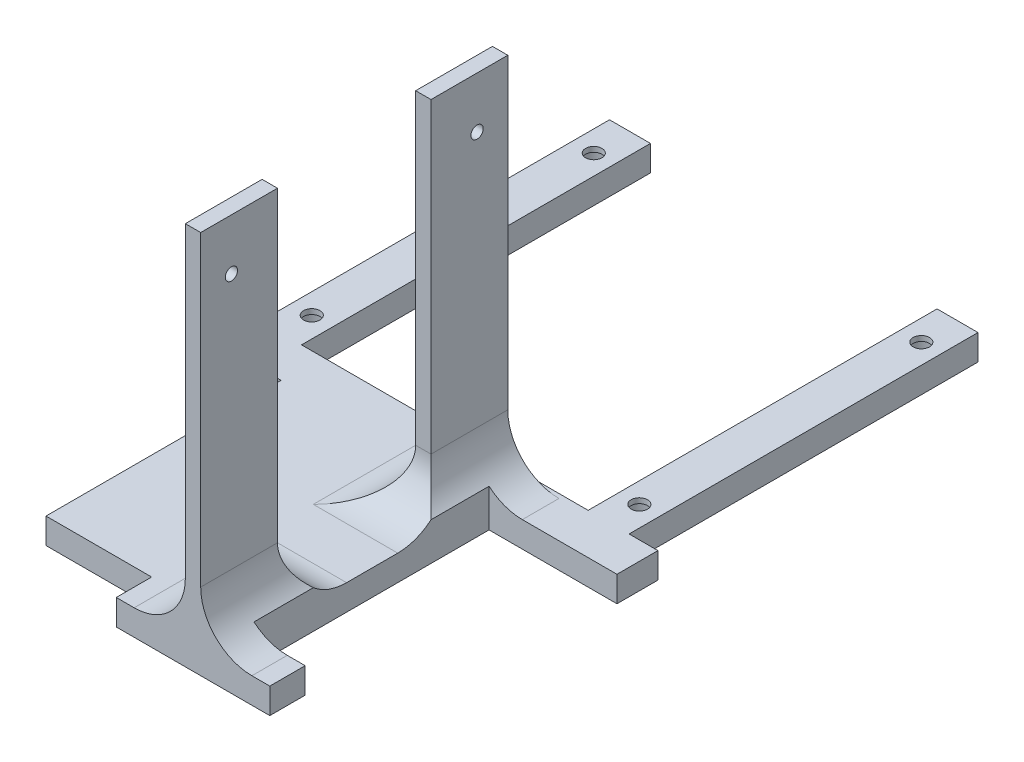
SolidWorks part; units mm, degrees
ref_plane "Front Plane" through (0, 0, 0) normal (0, 0, 1) x (1, 0, 0)
ref_plane "Top Plane" through (0, 0, 0) normal (0, 1, 0) x (1, 0, 0)
ref_plane "Right Plane" through (0, 0, 0) normal (1, 0, 0) x (0, 0, -1)
sketch "Sketch1" plane through (0, 0, 0) normal (0, 1, 0) x (1, 0, 0)
  line L0 (5, 22.8413) -> (16.3601, 22.8413)
  line L4 (5, 22.8413) -> (5, -23.0883)
  line L6 (-35.6399, 22.8413) -> (-35.6399, -23.0883)
  line L15 (-15, -30) -> (15, -30)
  line L16 (-15, -30) -> (-15, -23.0883)
  line L18 (15, -30) -> (15, -23.0883)
  line L19 (5, -23.0883) -> (15, -23.0883)
  line L20 (-35.6399, -23.0883) -> (-15, -23.0883)
  line L26 (-44.0081, 22.8413) -> (-35.6399, 22.8413)
  line L27 (16.3601, 22.8413) -> (29.9919, 22.8413)
  line L28 (29.9919, 22.8413) -> (29.9919, 30.01)
  line L29 (-44.0081, 22.8413) -> (-51.6409, 22.8413)
  line L30 (-51.6409, 22.8413) -> (-51.6409, 30.8413)
  line L31 (-51.6409, 30.8413) -> (-47.6409, 30.8413)
  line L32 (29.9919, 30.8413) -> (29.9919, 30.01)
  line L33 (-39.6409, 30.8413) -> (16.3601, 30.8413)
  line L35 (-47.6409, 30.8413) -> (-47.6409, 88.1003)
  line L37 (-39.6409, 30.8413) -> (-39.6409, 88.1003)
  line L39 (16.3601, 30.8413) -> (16.3601, 92.1003)
  line L41 (24.3591, 30.8413) -> (24.3591, 92.1003)
  line L42 (24.3591, 30.8413) -> (29.9919, 30.8413)
  line L46 (16.3601, 92.1003) -> (16.3601, 99.0177)
  line L47 (16.3601, 99.0177) -> (24.3591, 99.0177)
  line L48 (24.3591, 99.0177) -> (24.3591, 92.1003)
  line L49 (-47.6409, 88.1003) -> (-47.6409, 99.0177)
  line L50 (-47.6409, 99.0177) -> (-39.6409, 99.0177)
  line L51 (-39.6409, 99.0177) -> (-39.6409, 88.1003)
  circle A0 centre (-43.5402, 91.8413) radius 1.6
  circle A1 centre (20.4598, 91.8413) radius 1.6
  circle A2 centre (-43.6409, 36.8413) radius 1.6
  circle A3 centre (20.3591, 36.8413) radius 1.6
  point P0 (0, 0)
  dimension "D1" = 64
  dimension "D6" = 55
  dimension "D8" = 8
  dimension "D2" = 14
  dimension "D3" = 8
  dimension "D4" = 30
  dimension "D5" = 8
  dimension "D7" = 55
  dimension "D9" = 4
  dimension "D10" = 4
  dimension "D11" = 7.999
extrude "Boss-Extrude1" add sketch "Sketch1" along normal blind 5
sketch "Sketch5" plane through (0, 0, 0) normal (0, -1, 0) x (1, 0, 0)
  circle A0 centre (20.4598, -91.8413) radius 3
  circle A1 centre (20.3591, -36.8413) radius 3
  circle A2 centre (-43.5402, -91.8413) radius 3
  circle A3 centre (-43.6409, -36.8413) radius 3
extrude "Cut-Extrude6" cut sketch "Sketch5" against normal blind 4
sketch "Sketch2" plane through (0, 5, 0) normal (0, 1, 0) x (1, 0, 0)
  line L0 (-15, -30) -> (15, -30) construction
  line L1 (-1.5, -30) -> (1.5, -30)
  line L2 (-1.5, -30) -> (-1.5, -15)
  line L3 (-1.5, -15) -> (1.5, -15)
  line L4 (1.5, -30) -> (1.5, -15)
  line L5 (-55, 0) -> (55, 0) construction
  line L6 (-1.5, 15) -> (1.5, 15)
  line L7 (1.5, 30) -> (1.5, 15)
  line L8 (-1.5, 30) -> (1.5, 30)
  line L9 (-1.5, 30) -> (-1.5, 15)
  dimension "D1" = 15
  dimension "D2" = 3
  dimension "D3" = 13.5
extrude "Boss-Extrude2" add sketch "Sketch2" along normal blind 70
sketch "Sketch3" plane through (-1.5, 0, 0) normal (-1, 0, 0) x (0, 0, 1)
  line L1 (0, -55) -> (0, 55) construction
  line L5 (23.0883, 0) -> (30, 0) construction
  circle A0 centre (-24, 65) radius 1.2
  circle A1 centre (24, 65) radius 1.2
  dimension "D1" = 65
  dimension "D2" = 48
extrude "Cut-Extrude1" cut sketch "Sketch3" against normal blind 70
fillet "Fillet1" radius 10 6 edges at (0, 5, 15) (1.5, 5, -22.5) (1.5, 5, 22.5) (-1.5, 5, 22.5) (0, 5, -15) (-1.5, 5, -22.5)
